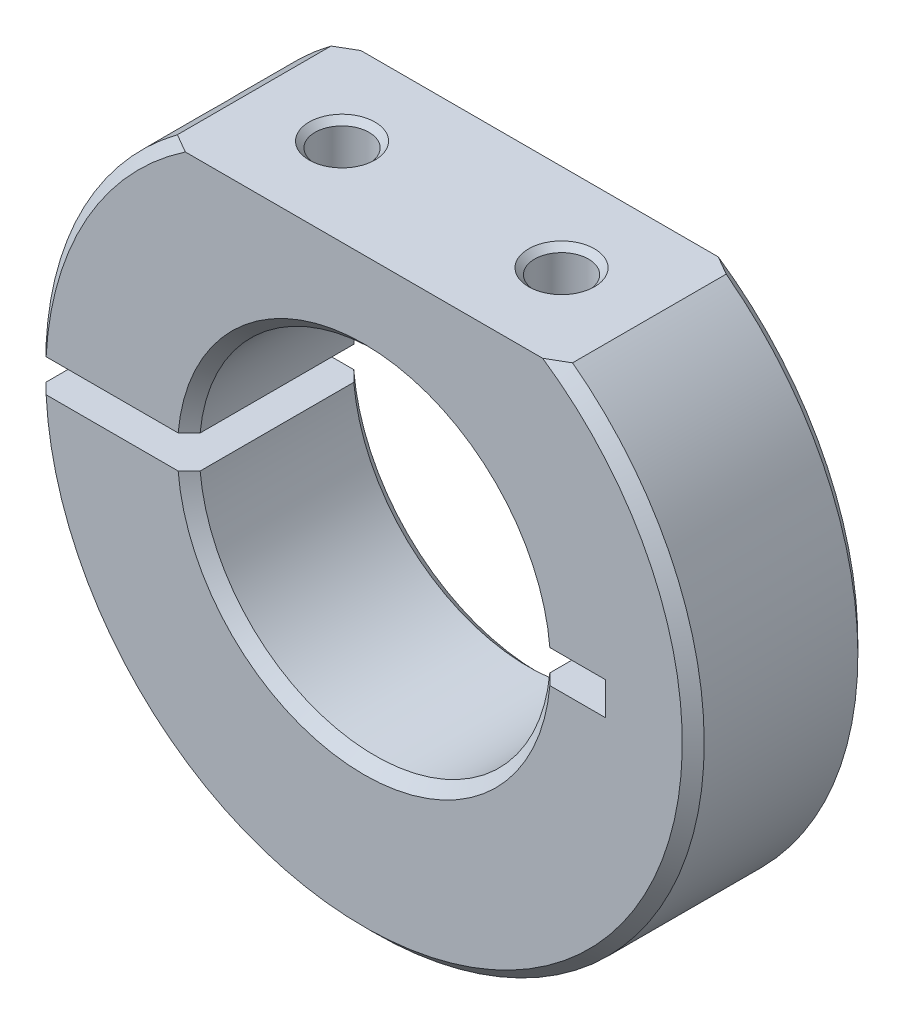
SolidWorks part; units mm, degrees
ref_plane "Front Plane" through (0, 0, 0) normal (0, 0, 1) x (1, 0, 0)
ref_plane "Top Plane" through (0, 0, 0) normal (0, 1, 0) x (1, 0, 0)
ref_plane "Right Plane" through (0, 0, 0) normal (1, 0, 0) x (0, 0, -1)
ref_plane "Plane1" through (0, 0, 0) normal (1, 0, 0) x (0, 0, -1)
sketch "Sketch1" plane through (0, 0, 0) normal (1, 0, 0) x (0, 0, -1)
  line L0 (-4, 8.5) -> (-3.5, 8)
  line L1 (-3.5, 8) -> (3.5, 8)
  line L2 (3.5, 8) -> (4, 8.5)
  line L3 (4, 8.5) -> (4, 14.5)
  line L4 (4, 14.5) -> (3.5, 15)
  line L5 (3.5, 15) -> (-3.5, 15)
  line L6 (-3.5, 15) -> (-4, 14.5)
  line L7 (-4, 14.5) -> (-4, 8.5)
  line L8 (4, 0) -> (-4, 0) construction
revolve "Revolve1" add sketch "Sketch1" angle 360 about L8 reverse direction yes
ref_plane "Plane2" through (0, 0, 0) normal (0, 0, 1) x (1, 0, 0)
sketch "Sketch2" plane through (0, 0, 0) normal (0, 0, 1) x (1, 0, 0)
  line L0 (-30, -0.75) -> (11, -0.75)
  line L1 (11, -0.75) -> (11, 0.75)
  line L2 (11, 0.75) -> (-30, 0.75)
  line L3 (-30, 0.75) -> (-30, -0.75)
extrude "Cut-Extrude1" cut sketch "Sketch2" against normal blind 4 and the other way blind 4
ref_plane "Plane3" through (0, 0, 0) normal (0, 0, 1) x (1, 0, 0)
sketch "Sketch3" plane through (0, 0, 0) normal (0, 0, 1) x (1, 0, 0)
  line L0 (-11.5, -15) -> (-14.5, -15)
  line L1 (-14.5, -15) -> (-14.5, -3)
  line L2 (-14.5, -3) -> (-13.2, -3)
  line L3 (-13.2, -3) -> (-13.2, 0)
  line L4 (-13.2, 0) -> (-11.5, 0)
  line L5 (-11.5, 0) -> (-11.5, -15)
  line L6 (-11.5, 0) -> (-11.5, -15) construction
revolve "Cut-Revolve1" cut sketch "Sketch3" angle 360 about L6
ref_plane "Plane4" through (0, 0, 0) normal (0, 0, 1) x (1, 0, 0)
sketch "Sketch4" plane through (0, 0, 0) normal (0, 0, 1) x (1, 0, 0)
  line L0 (-11.5, 0.75) -> (-12.7295, 0.75)
  line L1 (-12.7295, 0.75) -> (-12.7295, 15.75)
  line L2 (-12.7295, 15.75) -> (-11.5, 15.75)
  line L3 (-11.5, 15.75) -> (-11.5, 0.75)
  line L4 (-11.5, 15.75) -> (-11.5, 0.75) construction
revolve "Cut-Revolve2" cut sketch "Sketch4" angle 360 about L4
cosmetic thread "Cosmetic Thread1" parameters "D1"=8.8807, "D2"=3
ref_plane "Plane5" through (0, 0, 0) normal (0, 0, 1) x (1, 0, 0)
sketch "Sketch5" plane through (0, 0, 0) normal (0, 0, 1) x (1, 0, 0)
  line L0 (-15, 12) -> (15, 12)
  line L1 (15, 12) -> (15, 15.75)
  line L2 (15, 15.75) -> (-15, 15.75)
  line L3 (-15, 15.75) -> (-15, 12)
extrude "Cut-Extrude2" cut sketch "Sketch5" against normal blind 8 and the other way blind 8
ref_plane "Plane6" through (0, 0, 0) normal (0, 0, 1) x (1, 0, 0)
sketch "Sketch6" plane through (0, 0, 0) normal (0, 0, 1) x (1, 0, 0)
  line L0 (-5, 2.3333) -> (-6.2295, 2.3333)
  line L1 (-6.2295, 2.3333) -> (-6.2295, 11.7295)
  line L2 (-6.2295, 11.7295) -> (-6.5, 12)
  line L3 (-6.5, 12) -> (-5, 12)
  line L4 (-5, 12) -> (-5, 2.3333)
  line L5 (-5, 12) -> (-5, 2.3333) construction
revolve "Cut-Revolve3" cut sketch "Sketch6" angle 360 about L5
cosmetic thread "Cosmetic Thread2" parameters "D1"=4.8, "D2"=3
ref_plane "Plane7" through (0, 0, 0) normal (0, 0, 1) x (1, 0, 0)
sketch "Sketch7" plane through (0, 0, 0) normal (0, 0, 1) x (1, 0, 0)
  line L0 (5, 2.3333) -> (3.7705, 2.3333)
  line L1 (3.7705, 2.3333) -> (3.7705, 11.7295)
  line L2 (3.7705, 11.7295) -> (3.5, 12)
  line L3 (3.5, 12) -> (5, 12)
  line L4 (5, 12) -> (5, 2.3333)
  line L5 (5, 12) -> (5, 2.3333) construction
revolve "Cut-Revolve4" cut sketch "Sketch7" angle 360 about L5
cosmetic thread "Cosmetic Thread3" parameters "D1"=4.8, "D2"=3
